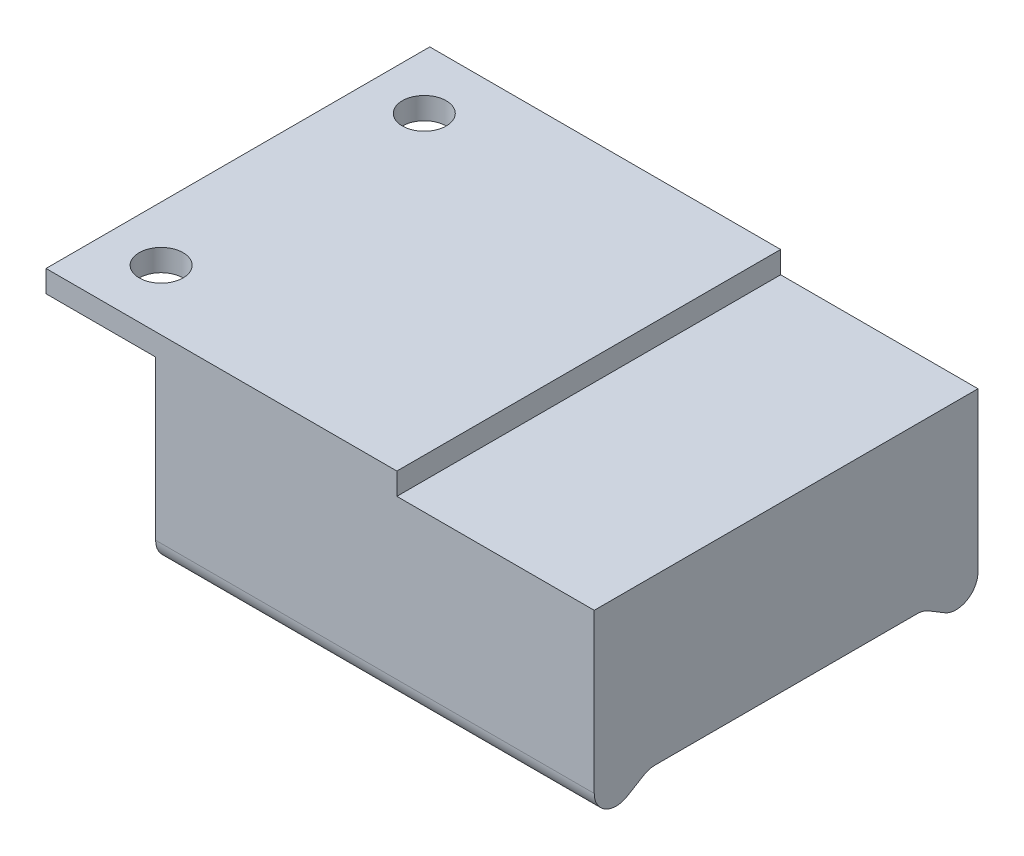
SolidWorks part; units mm, degrees
material "PEI"
ref_plane "Front Plane" through (0, 0, 0) normal (0, 0, 1) x (1, 0, 0)
ref_plane "Top Plane" through (0, 0, 0) normal (0, 1, 0) x (1, 0, 0)
ref_plane "Right Plane" through (0, 0, 0) normal (1, 0, 0) x (0, 0, -1)
sketch "Sketch1" plane through (0, 0, 0) normal (0, 1, 0) x (1, 0, 0)
  line L1 (20, -17.5) -> (-20, -17.5)
  line L2 (20, -17.5) -> (20, 17.5)
  line L3 (20, 17.5) -> (-20, 17.5)
  line L4 (-20, -17.5) -> (-20, 17.5)
  line L5 (20, -17.5) -> (-20, 17.5) construction
  line L6 (20, 17.5) -> (-20, -17.5) construction
  point P0 (0, 0)
  dimension "D1" = 35
  dimension "D2" = 40
extrude "Boss-Extrude1" add sketch "Sketch1" against normal blind 20
sketch "Sketch2" plane through (20, 0, 0) normal (1, 0, 0) x (0, 0, -1)
  line L0 (-17.5, -20) -> (-12.5, -17)
  line L1 (-12.5, -17) -> (12.5, -17)
  line L2 (0, -17) -> (0, -20)
  line L3 (17.5, -20) -> (12.5, -17)
  line L4 (17.5, 0) -> (-17.5, 0)
  line L5 (-17.5, 0) -> (-17.5, -20)
  line L6 (-17.5, -20) -> (17.5, -20)
  line L7 (17.5, -20) -> (17.5, 0)
  line L8 (17.5, 0) -> (-17.5, 0)
  line L9 (-17.5, 0) -> (-17.5, -20)
  line L10 (-17.5, -20) -> (17.5, -20)
  line L11 (17.5, -20) -> (17.5, 0)
  line M7 (-17.5, -20) -> (17.5, -20)
  dimension "D2" = 5
  dimension "D3" = 3
  dimension "D1" = 0
extrude "Cut-Extrude1" cut sketch "Sketch2" against normal through all and the other way through all contours L2 L1 L0 M7 | L3 L1 L2 M7 region at (20, -18.5833, 7.5694) region at (20, -18.5833, -7.5694)
fillet "Fillet1" radius 2 4 edges at (0, -17, 12.5) (0, -17, -12.5) (0, -20, -17.5) (0, -20, 17.5)
sketch "Sketch5" plane through (-20, 0, 0) normal (-1, 0, 0) x (0, 0, 1)
  line L1 (-17.5, 0) -> (17.5, 0)
  line L2 (-17.5, 0) -> (-17.5, -2)
  line L3 (-17.5, -2) -> (17.5, -2)
  line L4 (17.5, 0) -> (17.5, -2)
  line L6 (-17.5, 0) -> (-17.5, -16.4676)
  line L7 (-14.471, -18.1826) -> (-12.975, -17.285)
  line L8 (-11.946, -17) -> (11.946, -17)
  line L9 (12.975, -17.285) -> (14.471, -18.1826)
  line L10 (17.5, -16.4676) -> (17.5, 0)
  line L11 (17.5, 0) -> (-17.5, 0)
  line L12 (-17.5, 0) -> (-17.5, -16.4676)
  line L13 (-14.471, -18.1826) -> (-12.975, -17.285)
  line L14 (-11.946, -17) -> (11.946, -17)
  line L15 (12.975, -17.285) -> (14.471, -18.1826)
  line L16 (17.5, -16.4676) -> (17.5, 0)
  line L22 (17.5, 0) -> (-17.5, 0)
  arc A4 (-17.5, -16.4676) -> (-14.471, -18.1826) centre (-15.5, -16.4676) ccw
  arc A5 (-17.5, -16.4676) -> (-14.471, -18.1826) centre (-15.5, -16.4676) ccw
  arc A6 (-11.946, -17) -> (-12.975, -17.285) centre (-11.946, -19) ccw
  arc A7 (-11.946, -17) -> (-12.975, -17.285) centre (-11.946, -19) ccw
  arc A12 (12.975, -17.285) -> (11.946, -17) centre (11.946, -19) ccw
  arc A13 (12.975, -17.285) -> (11.946, -17) centre (11.946, -19) ccw
  arc A14 (14.471, -18.1826) -> (17.5, -16.4676) centre (15.5, -16.4676) ccw
  arc A15 (14.471, -18.1826) -> (17.5, -16.4676) centre (15.5, -16.4676) ccw
  line M13 (-17.5, 0) -> (-17.5, -16.4676)
  line M21 (17.5, -16.4676) -> (17.5, 0)
  line M22 (17.5, 0) -> (-17.5, 0)
  dimension "D2" = 2
  dimension "D1" = 0
sketch "Sketch6"
  line L0 (0, 0) -> (40, 0)
  line L1 (20, 17.5) -> (40, 17.5)
  line L2 (20, -17.5) -> (40, -17.5)
  line L4 (-20, 17.5) -> (-20, -17.5)
  line L5 (-20, -17.5) -> (20, -17.5)
  line L6 (20, -17.5) -> (20, 17.5)
  line L7 (20, 17.5) -> (-20, 17.5)
  line L8 (-20, 17.5) -> (-20, -17.5)
  line L9 (-20, -17.5) -> (20, -17.5)
  line L10 (20, -17.5) -> (20, 17.5)
  line L11 (20, 17.5) -> (-20, 17.5)
  circle A0 centre (40, 12) radius 4.25
  circle A2 centre (40, 0) radius 17.5
  circle A4 centre (40, 0) radius 12
  circle A5 centre (52, 0) radius 4.25
  circle A7 centre (40, 0) radius 9
  circle A8 centre (40, 12) radius 2
  circle A9 centre (52, 0) radius 2
  circle A13 centre (40, -12) radius 4.25
  circle A14 centre (28, 0) radius 4.25
  circle A15 centre (28, 0) radius 2
  circle A16 centre (40, -12) radius 2
  point P8 (28, 0)
  dimension "D3" = 8.5
  dimension "D4" = 8.5
  dimension "D5" = 8.5
  dimension "D6" = 8.5
  dimension "D7" = 24
  dimension "D8" = 18
  dimension "D9" = 4
  dimension "D10" = 4
  dimension "D11" = 4
  dimension "D12" = 4
  dimension "D2" = 40
  dimension "D1" = 0
sketch "Sketch6<7>" plane through (0, 0, 0) normal (0, 1, 0) x (1, 0, 0) same geometry as "Sketch6"
sketch "Sketch7" plane through (0, 0, 0) normal (0, 1, 0) x (1, 0, 0)
  line L0 (24, -17.5) -> (24, -14.5)
  line L1 (24, -14.5) -> (34, -14.5)
  line L2 (34, -14.5) -> (34, -17.5)
  line L6 (-20, 17.5) -> (-20, -17.5)
  line L7 (-20, -17.5) -> (40, -17.5)
  line L12 (-20, 17.5) -> (-20, -17.5)
  line L13 (-20, -17.5) -> (40, -17.5)
  line L14 (40, 17.5) -> (-20, 17.5)
  line L15 (-20, 17.5) -> (-20, -17.5)
  line L16 (-20, -17.5) -> (40, -17.5)
  line L17 (40, 17.5) -> (-20, 17.5)
  arc A3 (40, -17.5) -> (40, 17.5) centre (40, 0) ccw
  arc A4 (40, -17.5) -> (40, 17.5) centre (40, 0) ccw
  dimension "D2" = 10
  dimension "D3" = 3
  dimension "D4" = 44
  dimension "D5" = 0
sketch "Sketch8" plane through (0, 0, 17.5) normal (0, 0, 1) x (1, 0, 0)
  line L1 (2, 0) -> (22, 0)
  line L2 (2, 0) -> (2, -2)
  line L3 (2, -2) -> (22, -2)
  line L4 (22, 0) -> (22, -2)
  line L10 (34, -3) -> (24, -3)
  line L11 (24, -3) -> (24, 0)
  line L12 (24, 0) -> (-20, 0)
  line L13 (-20, 0) -> (-20, -16.4676)
  line L14 (-20, -16.4676) -> (20, -16.4676)
  line L15 (20, -16.4676) -> (20, -17)
  line L16 (20, -17) -> (40, -17)
  line L17 (40, -17) -> (40, 0)
  line L18 (40, 0) -> (34, 0)
  line L19 (34, 0) -> (34, -3)
  line L20 (34, -3) -> (24, -3)
  line L22 (24, 0) -> (-20, 0)
  line L23 (-20, 0) -> (-20, -16.4676)
  line L24 (-20, -16.4676) -> (20, -16.4676)
  line L25 (20, -16.4676) -> (20, -17)
  line L26 (20, -17) -> (40, -17)
  line L27 (40, -17) -> (40, 0)
  line L28 (40, 0) -> (34, 0)
  line L34 (24, -3) -> (24, 0)
  line L35 (34, 0) -> (34, -3)
  line M15 (24, 0) -> (-20, 0)
  dimension "D2" = 2
  dimension "D3" = 20
  dimension "D4" = 22
  dimension "D1" = 0
extrude "Cut-Extrude5" cut sketch "Sketch8" against normal through all contours L4 L2 L3 M15 region at (12, -1, 17.5)
extrude "Boss-Extrude3" add sketch "Sketch5" along normal blind 10 contours L3 M13 M21 M22 region at (-20, -1, 0)
sketch "Sketch12" plane through (0, 0, 0) normal (0, 1, 0) x (1, 0, 0)
  line L0 (0, 0) -> (-25, 0)
  line L1 (-25, 0) -> (-25, 12)
  line L4 (2, -17.5) -> (2, 17.5)
  line L5 (2, 17.5) -> (-30, 17.5)
  line L6 (-30, 17.5) -> (-30, -17.5)
  line L7 (-30, -17.5) -> (2, -17.5)
  line L8 (2, -17.5) -> (2, 17.5)
  line L9 (2, 17.5) -> (-30, 17.5)
  line L10 (-30, 17.5) -> (-30, -17.5)
  line L11 (-30, -17.5) -> (2, -17.5)
  line L14 (2, -17.5) -> (2, 17.5)
  line L15 (2, 17.5) -> (-30, 17.5)
  line L17 (-30, -17.5) -> (2, -17.5)
  line L18 (2, -17.5) -> (2, 17.5)
  line L20 (-30, 17.5) -> (-30, -17.5)
  line L21 (-30, 17.5) -> (-30, -17.5)
  line L22 (2, 17.5) -> (-30, 17.5)
  line L24 (-30, -17.5) -> (2, -17.5)
  circle A0 centre (-25, 12) radius 2
  circle A1 centre (-25, -12) radius 2
  dimension "D5" = 4
  dimension "D4" = 12
  dimension "D1" = 0
  dimension "D2" = 0
extrude "Cut-Extrude7" cut sketch "Sketch12" against normal through all contours A0 | A1 region at (-23.6258, 0, -10.6258) region at (-25, 0, 12)
